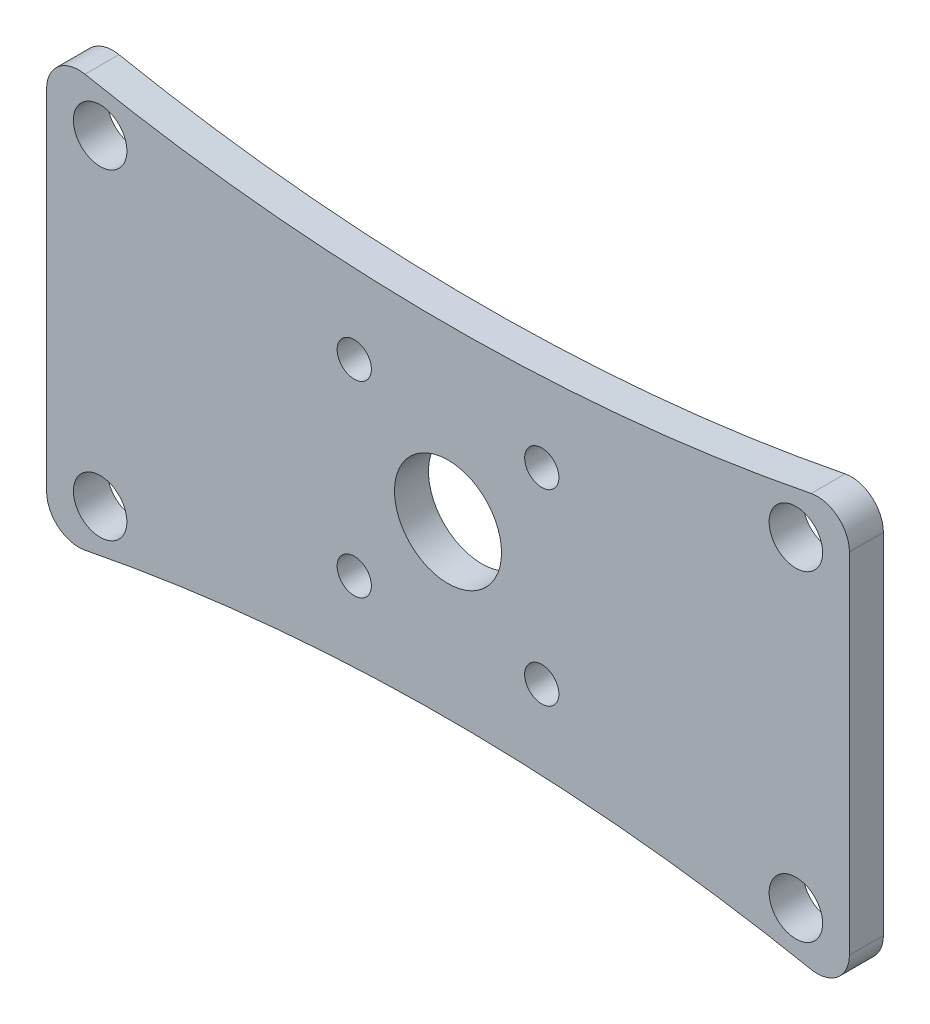
SolidWorks part; units mm, degrees
ref_plane "Front Plane" through (0, 0, 0) normal (0, 0, 1) x (1, 0, 0)
ref_plane "Top Plane" through (0, 0, 0) normal (0, 1, 0) x (1, 0, 0)
ref_plane "Right Plane" through (0, 0, 0) normal (1, 0, 0) x (0, 0, -1)
sketch "Sketch1" plane through (0, 0, 0) normal (0, 0, 1) x (1, 0, 0)
  line L0 (-37.5, 20) -> (37.5, -20) construction
  line L1 (-37.5, 20) -> (37.5, 20)
  line L2 (-37.5, 20) -> (-37.5, -20)
  line L3 (-37.5, -20) -> (37.5, -20)
  line L4 (37.5, 20) -> (37.5, -20)
  line L5 (-32.5, 15) -> (32.5, -15) construction
  line L6 (-32.5, 15) -> (32.5, 15) construction
  line L7 (-32.5, 15) -> (-32.5, -15) construction
  line L8 (-32.5, -15) -> (32.5, -15) construction
  line L9 (32.5, 15) -> (32.5, -15) construction
  line L10 (-8.76, 8.76) -> (8.76, -8.76) construction
  line L11 (-8.76, 8.76) -> (8.76, 8.76) construction
  line L12 (-8.76, 8.76) -> (-8.76, -8.76) construction
  line L13 (-8.76, -8.76) -> (8.76, -8.76) construction
  line L14 (8.76, 8.76) -> (8.76, -8.76) construction
  circle A0 centre (-32.5, 15) radius 2.5
  circle A1 centre (32.5, 15) radius 2.5
  circle A2 centre (32.5, -15) radius 2.5
  circle A3 centre (-32.5, -15) radius 2.5
  circle A4 centre (-8.76, 8.76) radius 1.6
  circle A5 centre (8.76, 8.76) radius 1.6
  circle A6 centre (8.76, -8.76) radius 1.6
  circle A7 centre (-8.76, -8.76) radius 1.6
  point P4 (0, 0)
  point P10 (0, 0)
  point P23 (0, 0)
  dimension "D5" = 5
  dimension "D7" = 3.2
  dimension "D1" = 40
  dimension "D2" = 75
  dimension "D3" = 30
  dimension "D4" = 65
  dimension "D6" = 17.52
extrude "Boss-Extrude1" add sketch "Sketch1" along normal blind 3.175
sketch "Sketch2" plane through (0, 0, 3.175) normal (0, 0, 1) x (1, 0, 0)
  circle A0 centre (0, 190.9349) radius 175
  circle A1 centre (0, -190.9349) radius 175
  dimension "D1" = 350
extrude "Cut-Extrude1" cut sketch "Sketch2" against normal blind 3.175
fillet "Fillet1" radius 3 4 edges at (37.5, 20, 1.5875) (37.5, -20, 1.5875) (-37.5, -20, 1.5875) (-37.5, 20, 1.5875)
sketch "Sketch3" plane through (0, 0, 3.175) normal (0, 0, 1) x (1, 0, 0)
  circle A0 centre (0, 0) radius 5
  dimension "D1" = 10
extrude "Cut-Extrude2" cut sketch "Sketch3" against normal blind 3.175
